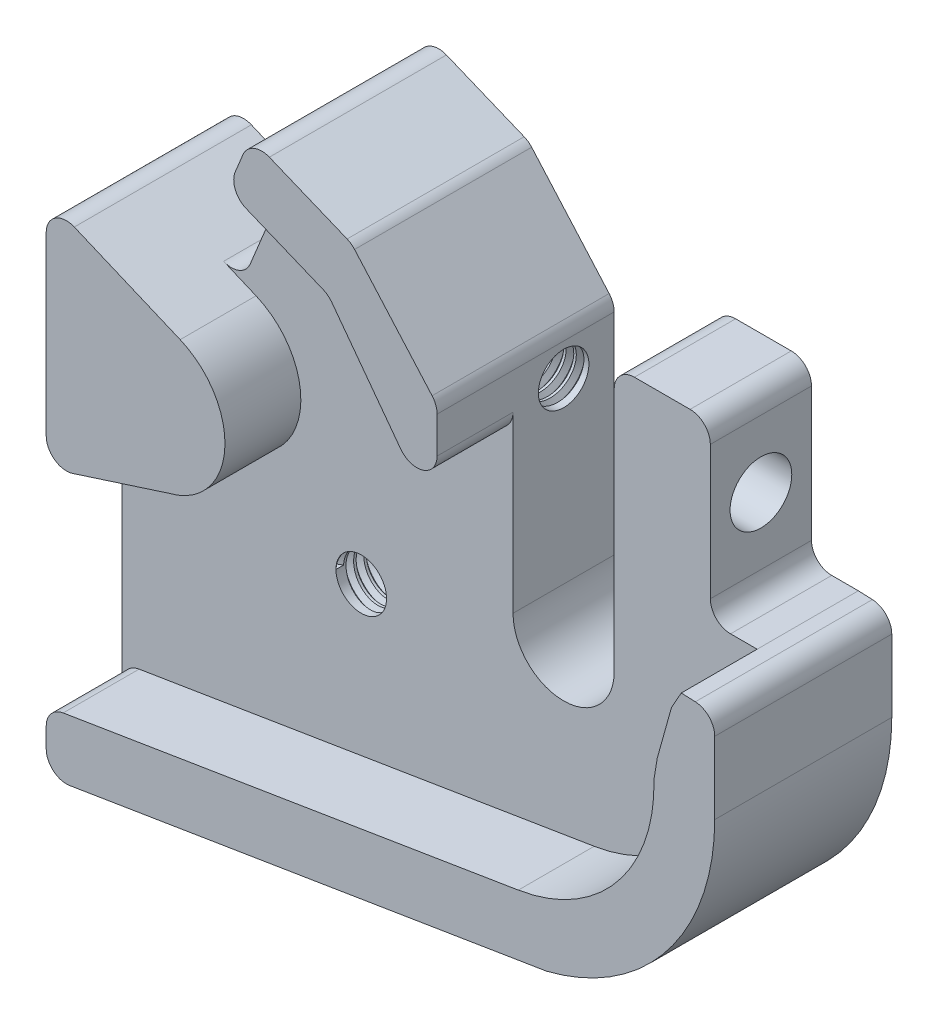
SolidWorks part; units mm, degrees
ref_plane "Front Plane" through (0, 0, 0) normal (0, 0, 1) x (1, 0, 0)
ref_plane "Top Plane" through (0, 0, 0) normal (0, 1, 0) x (1, 0, 0)
ref_plane "Right Plane" through (0, 0, 0) normal (1, 0, 0) x (0, 0, -1)
sketch "Sketch1" plane through (0, 0, 0) normal (0, 0, 1) x (1, 0, 0)
  line L0 (-48.8998, -64.1664) -> (-34.4801, 53.9567) construction
  line L3 (0, 51.4823) -> (78.4652, 51.4823)
  line L4 (78.4652, 0) -> (78.4652, 51.4823)
  line L5 (-0.9054, 14.8469) -> (9.0946, 14.8469)
  line L6 (9.0946, 14.8469) -> (9.0946, -2.1531)
  line L7 (9.0946, -2.1531) -> (-0.9054, -2.1531)
  line L8 (-0.9054, -2.1531) -> (-0.9054, 14.8469)
  line L9 (-11.6542, 28.4583) -> (-0.9054, 14.02)
  line L10 (-52.5896, 45.2866) -> (-11.6542, 28.4583)
  line L11 (9.0946, 14.8469) -> (9.0946, 29.052)
  line L12 (9.0946, 29.052) -> (18.5946, 29.052)
  line L13 (-61.5112, 32.1478) -> (-26.3036, 17.3197)
  line L14 (-26.3036, 17.3197) -> (-29.1124, 10.6505)
  line L15 (-29.1124, 10.6505) -> (-31.9213, 3.9813)
  line L16 (-70.304, -10.1797) -> (-26.4323, 3.9286)
  line L17 (-39.5424, 22.8954) -> (-39.5424, -0.2874)
  line L18 (-26.4323, 3.9286) -> (-29.1124, 10.6505)
  line L19 (-29.1124, 10.6505) -> (-31.7926, 17.3724)
  line L20 (-74.2907, -26.3461) -> (-1.036, -14.4136)
  line L21 (-1.036, -14.4136) -> (7.1186, -13.0853)
  line L22 (23.2246, 11.8381) -> (22.2572, 10.123)
  line L23 (23.2246, 11.8381) -> (34.7443, 11.3546)
  line L24 (-0.9054, 14.8469) -> (-0.9054, 20.5391)
  line L25 (-19.3381, 38.1043) -> (-8.9222, 33.8224)
  line L26 (-11.6542, 28.4583) -> (-9.3728, 34.0076)
  line L27 (-7.3088, 22.6214) -> (-2.496, 26.2043)
  line L28 (-2.496, 26.2043) -> (-9.3728, 34.0076)
  line L29 (-70.3938, -25.7113) -> (-69.6167, -30.4821)
  line L30 (-39.5424, -20.686) -> (-39.5424, -26.686)
  line L31 (26.529, 2.6512) -> (26.529, -15.9236)
  line L32 (27.019, 6.583) -> (34.7443, 6.583)
  line L33 (34.7443, 6.583) -> (34.7443, 11.3546)
  line L34 (-11.6542, 28.4583) -> (-8.9222, 28.4583)
  line L35 (-70.3938, -25.7113) -> (-70.304, -10.1797)
  line L36 (18.5946, 29.052) -> (18.5946, 11.8381)
  line L37 (-39.5424, -0.2874) -> (-39.5424, -20.686)
  line L38 (-39.5424, 22.8954) -> (-39.5424, 39.923)
  line L39 (22.2572, 10.123) -> (21.4546, 7.2463)
  line L40 (21.4546, 7.2463) -> (20.8501, 5.08)
  line L41 (20.8501, 5.08) -> (20.5233, 3.0772)
  line L42 (-8.9222, 28.4583) -> (-8.9222, 25.2921)
  line L43 (-19.3381, 38.1043) -> (-21.6194, 32.5549)
  line L44 (-0.9054, 20.5391) -> (-0.9054, 24.0677)
  line L45 (-2.496, 26.2043) -> (-0.9054, 24.3993)
  line L46 (-21.6194, 32.5549) -> (-27.6495, 17.8865)
  line L47 (-39.5424, -26.686) -> (29.4812, -15.4427)
  line L48 (4.5907, 2.6512) -> (20.529, 2.6512) construction
  line L49 (20.529, 2.6512) -> (26.529, 2.6512) construction
  line L50 (26.529, 2.6512) -> (26.529, 6.583)
  line L51 (26.529, 6.583) -> (27.019, 6.583)
  line L52 (-0.9054, 24.3993) -> (-0.9054, 24.0677)
  line L53 (18.5946, 11.8381) -> (23.2246, 11.8381)
  line L54 (4.0946, -2.1531) -> (-15.9054, -2.1531)
  line L55 (26.529, 6.583) -> (26.529, 11.6994)
  circle A0 centre (4.0946, 2.8469) radius 5
  circle A1 centre (4.0946, 9.8469) radius 5
  circle A2 centre (-29.1124, 10.6505) radius 7.2365
  circle A3 centre (4.5907, 2.6512) radius 15.9383
  circle A4 centre (4.5907, 2.6512) radius 21.9383
  circle A5 centre (-15.9054, -2.1531) radius 3
  dimension "D4" = 9.5
  dimension "D7" = 6
  dimension "D1" = 119
  dimension "D2" = 10
  dimension "D3" = 17
  dimension "D5" = 18
  dimension "D6" = 6
extrude "Boss-Extrude2" add sketch "Sketch1" along normal blind 10 contours A5 A4 L9 L10 L46 L13 A2 L16 L37 L20 | A2 L13 L17 L16 | L25 L43 L10 L26 | L27 L28 L26 L9 | A4 L44 L52 L45 L27 L9 | A5 L54 A3 L9 A4 | A5 A4 L20 L21 A3 L54 | A3 L11 L6 L7 L54 | L9 A3 L54 L8 | A0 L8 L7 | A0 L7 L6 | L44 A4 L9 A3 L24 | L24 A3 L9 L8 | L36 A4 L11 A3 L41 L40 L39 L22 L53 | A4 L36 L12 L11 | L20 A4 L47 L23 L22 L39 L40 L41 A3 L21 | A4 L20 L30 L47 | A4 A5 | A5 A4 | A4 L50 L55 L23 | A2 region at (-1.579, 16.1313, 0) region at (-5.5514, 5.8811, 0) region at (-2.9873, 20.47, 0) region at (9.5356, 16.3934, 0) region at (-11.4558, 10.3377, 0) region at (15.4515, 16.6771, 0) region at (7.9778, -1.0363, 0) region at (0.2115, -1.0363, 0) region at (-23.7133, 1.7412, 0) region at (-3.9237, 23.8565, 0) region at (-8.3873, -9.8482, 0) region at (14.3748, 25.5507, 0) region at (21.1435, 4.0041, 0) region at (-7.5395, 27.8934, 0) region at (-15.0859, -1.961, 0) region at (-17.5867, -2.5472, 0) region at (-15.4961, 33.2813, 0) region at (25.9377, 9.4895, 0) region at (-20.9546, -20.8236, 0) region at (-36.3421, 11.3624, 0)
extrude "Boss-Extrude3" add sketch "Sketch1<7>" along normal blind 17.5 contours A2 L13 L17 L16 | L25 L43 L10 L26 | L27 L28 L26 L9 | A4 L44 L27 L9 | L44 A4 L9 A3 L24 | L24 A3 L9 L8 | A4 L20 L30 L47 | L20 A4 L47 L23 L22 L39 L40 L41 A3 L21 | A4 L50 L55 L23 | A2 region at (-1.579, 16.1313, 0) region at (-2.9873, 20.47, 0) region at (-3.9237, 23.8565, 0) region at (21.1435, 4.0041, 0) region at (-7.5395, 27.8934, 0) region at (-15.4961, 33.2813, 0) region at (25.9377, 9.4895, 0) region at (-20.9546, -20.8236, 0) region at (-36.3421, 11.3624, 0)
sketch "Sketch1<7>" plane through (0, 0, 0) normal (0, 0, 1) x (1, 0, 0) same geometry as "Sketch1"
sketch "Sketch2" plane through (18.5946, 0, 0) normal (1, 0, 0) x (0, 0, -1)
  line L0 (-5, 29.052) -> (-5, 20.445) construction
  line L1 (-10, 29.052) -> (0, 29.052) construction
  line L2 (-10, 20.445) -> (-5, 20.445) construction
  line L3 (-10, 29.052) -> (-10, 11.8381) construction
  circle A0 centre (-5, 20.445) radius 3.05
  dimension "D1" = 6.1
hole_wizard "Tap Drill for M6x1.0 Tap3" positions "3DSketch3" profile "Sketch7" hole size "M6x1.0" standard "ANSI Metric"
sketch3d "3DSketch3"
  point P0 (18.5946, 20.445, 5)
sketch "Sketch7" plane through (18.5946, 20.445, 5) normal (0, 1, 0) x (0, 0, -1)
  line L0 (0, 0) -> (0, 44.5022)
  line L1 (0, 44.5022) -> (2.5, 43)
  line L2 (2.5, 43) -> (2.5, 0)
  line L5 (2.5, 0) -> (0, 0)
  line L10 (0, 44.5022) -> (-2.5, 43) construction
  line L11 (0, -6.35) -> (0, 107.95) construction
  dimension "Hole Dia." = 5
  dimension "Hole Depth" = 43
  dimension "Drill Angle" = 118
fillet "Fillet1" radius 2 15 edges at (-39.5424, -20.686, 13.75) (-39.5424, -0.2874, 13.75) (-39.5424, -26.686, 8.75) (-0.9054, 14.02, 13.75) (-21.6194, 32.5549, 13.75) (-19.3381, 38.1043, 8.75) (-39.5424, 22.8954, 8.75) (-27.6495, 17.8865, 5) (-9.3728, 34.0076, 8.75) (9.0946, 29.052, 5) (18.5946, 29.052, 5) (18.5946, 11.8381, 5) (-0.9054, 24.3993, 8.75) (-11.6542, 28.4583, 13.75) (26.529, 11.6994, 8.75)
hole_wizard "Tap Drill for M6x1.0 Tap2" positions "3DSketch2" profile "Sketch5" hole size "M6x1.0" standard "ANSI Metric" end condition through all
sketch3d "3DSketch2"
  line L0 (4.0946, -2.1531, 10) -> (-15.9054, -2.1531, 10)
  arc A0 (-0.9054, 2.8469, 10) -> (9.0946, 2.8469, 10) centre (4.0946, 2.8469, 10) ccw construction
  point P0 (-15.9054, -2.1531, 10)
  point P8 (4.0946, 2.8469, 15)
  dimension "D1" = 20
sketch "Sketch5" plane through (-15.9054, -2.1531, 10) normal (1, 0, 0) x (0, -1, 0)
  line L0 (0, 0) -> (0, 10)
  line L1 (0, 10) -> (2.5, 10)
  line L2 (2.5, 10) -> (2.5, 0)
  line L5 (2.5, 0) -> (0, 0)
  line L11 (0, -6.35) -> (0, 107.95) construction
  dimension "Thru Hole Dia." = 5
  dimension "Thru Hole Depth" = 10
thread "Thread1" pitch 1 method cut profile "Thread Profile2" start angle 0, offset 0, length 23, pitch 1, diameter 5
ref_plane "Plane2" through (-0.9054, 20.445, 7.5) normal (0, -1, 0) x (0, 0, 1)
sketch "Thread Profile2" plane through (-0.9054, 20.445, 7.5) normal (0, -1, 0) x (0, 0, 1)
  line L0 (0, 0) -> (0, 1) construction
  line L1 (0, 0) -> (0.5413, 0.3125)
  line L2 (0.5413, 0.3125) -> (0.5413, 0.4375)
  line L3 (0.5413, 0.4375) -> (0, 0.75)
  line L4 (0.5413, 0.375) -> (0, 0.375) construction
  line L11 (0, 0) -> (0, 0.75)
  point P2 (0, 0)
  dimension "Pitch" = 1
  dimension "Profile_Angle" = 60
  dimension "Profile_Land" = 0.125
  dimension "Profile_Height" = 0.5413
extrude "Cut-Extrude2" cut sketch "Sketch2" against normal blind 10 contours A0
thread "Thread2" pitch 1 method cut profile "Thread Profile3" start angle 0, offset 0, length 13, pitch 1, diameter 5
ref_plane "Plane3" through (-18.4054, -2.1531, 10) normal (0, -1, 0) x (-1, 0, 0)
sketch "Thread Profile3" plane through (-18.4054, -2.1531, 10) normal (0, -1, 0) x (-1, 0, 0)
  line L0 (0, 0) -> (0, 1) construction
  line L1 (0, 0) -> (0.5413, 0.3125)
  line L2 (0.5413, 0.3125) -> (0.5413, 0.4375)
  line L3 (0.5413, 0.4375) -> (0, 0.75)
  line L4 (0.5413, 0.375) -> (0, 0.375) construction
  line L11 (0, 0) -> (0, 0.75)
  point P2 (0, 0)
  dimension "Pitch" = 1
  dimension "Profile_Angle" = 60
  dimension "Profile_Land" = 0.125
  dimension "Profile_Height" = 0.5413
